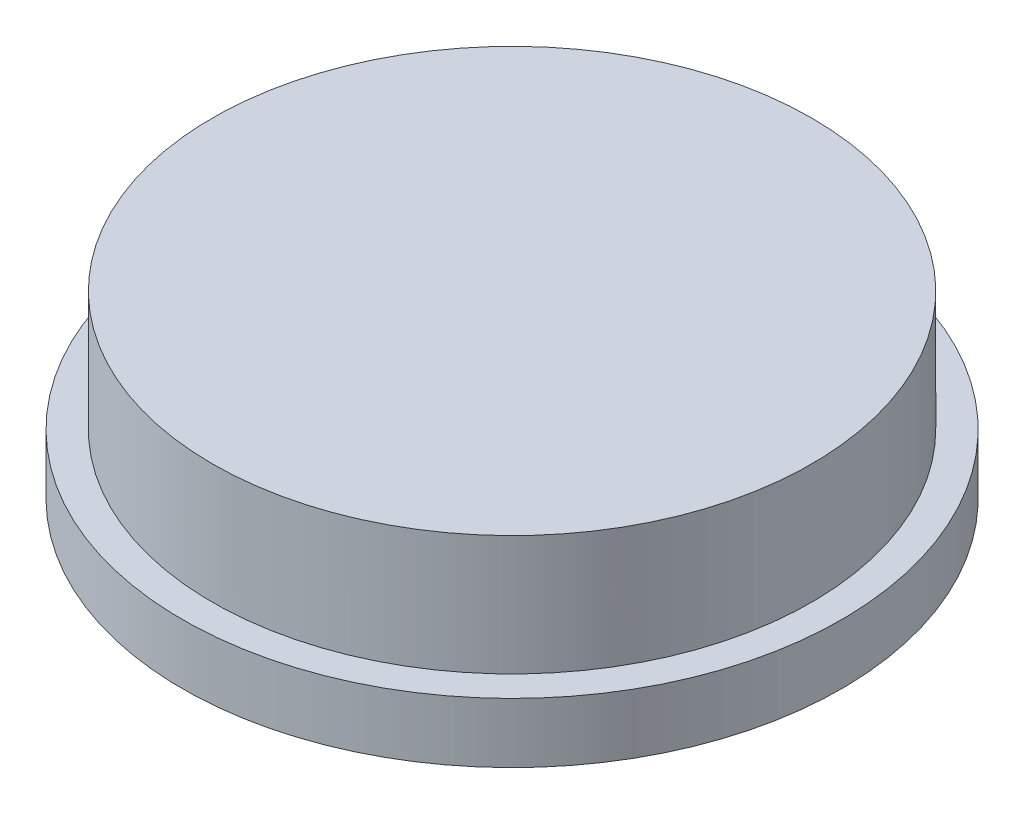
SolidWorks part; units mm, degrees
ref_plane "Front Plane" through (0, 0, 0) normal (0, 0, 1) x (1, 0, 0)
ref_plane "Top Plane" through (0, 0, 0) normal (0, 1, 0) x (1, 0, 0)
ref_plane "Right Plane" through (0, 0, 0) normal (1, 0, 0) x (0, 0, -1)
sketch "Sketch1" plane through (0, 0, 0) normal (0, 1, 0) x (1, 0, 0)
  circle A0 centre (0, 0) radius 10
  dimension "D1" = 20
extrude "Boss-Extrude1" add sketch "Sketch1" along normal blind 6
sketch "Sketch4" plane through (0, 0, 0) normal (0, -1, 0) x (1, 0, 0)
  circle A0 centre (0, 0) radius 11
  dimension "D1" = 22
extrude "Boss-Extrude2" add sketch "Sketch4" against normal blind 2
sketch "Sketch3" plane through (0, 0, 0) normal (0, 1, 0) x (1, 0, 0)
  line L0 (0, 8.0571) -> (0, -8.4294) construction
  line L2 (3.0311, 0) -> (1.5155, 2.625)
  line L3 (1.5155, 2.625) -> (-1.5155, 2.625)
  line L4 (-1.5155, 2.625) -> (-3.0311, 0)
  line L5 (-3.0311, 0) -> (-1.5155, -2.625)
  line L6 (-1.5155, -2.625) -> (1.5155, -2.625)
  line L7 (1.5155, -2.625) -> (3.0311, 0)
  circle A2 centre (0, 0) radius 5.5 construction
  circle A3 centre (0, 0) radius 2.625 construction
  dimension "D1" = 11
  dimension "D2" = 5.25
extrude "Cut-Extrude2" cut sketch "Sketch3" along normal blind 5
